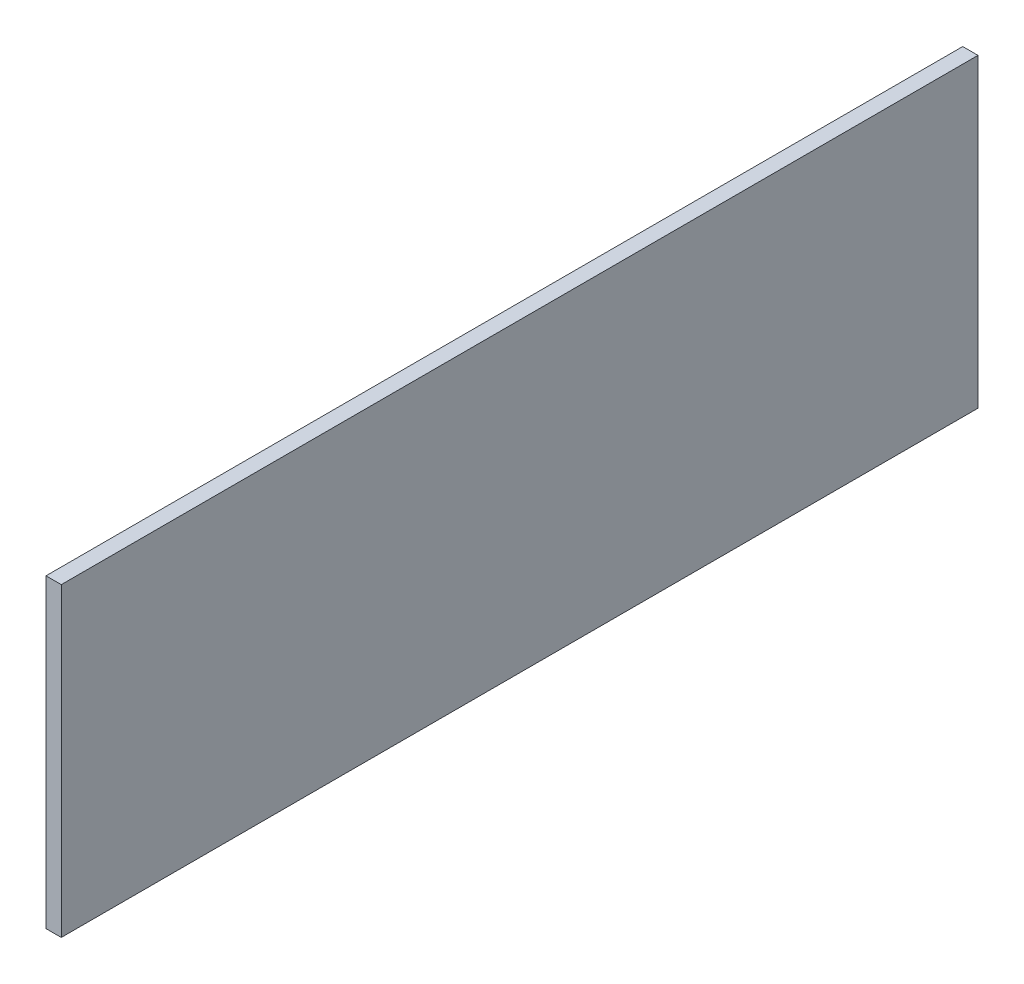
SolidWorks part; units mm, degrees
ref_plane "Front Plane" through (0, 0, 0) normal (0, 0, 1) x (1, 0, 0)
ref_plane "Top Plane" through (0, 0, 0) normal (0, 1, 0) x (1, 0, 0)
ref_plane "Right Plane" through (0, 0, 0) normal (1, 0, 0) x (0, 0, -1)
sketch "Sketch1" plane through (0, 0, 0) normal (1, 0, 0) x (0, 0, -1)
  line L1 (-551.8519, 418.0556) -> (648.1481, 418.0556)
  line L2 (-551.8519, 418.0556) -> (-551.8519, 18.0556)
  line L3 (-551.8519, 18.0556) -> (648.1481, 18.0556)
  line L4 (648.1481, 418.0556) -> (648.1481, 18.0556)
  dimension "D1" = 1200
  dimension "D2" = 400
extrude "Boss-Extrude1" add sketch "Sketch1" along normal blind 20
